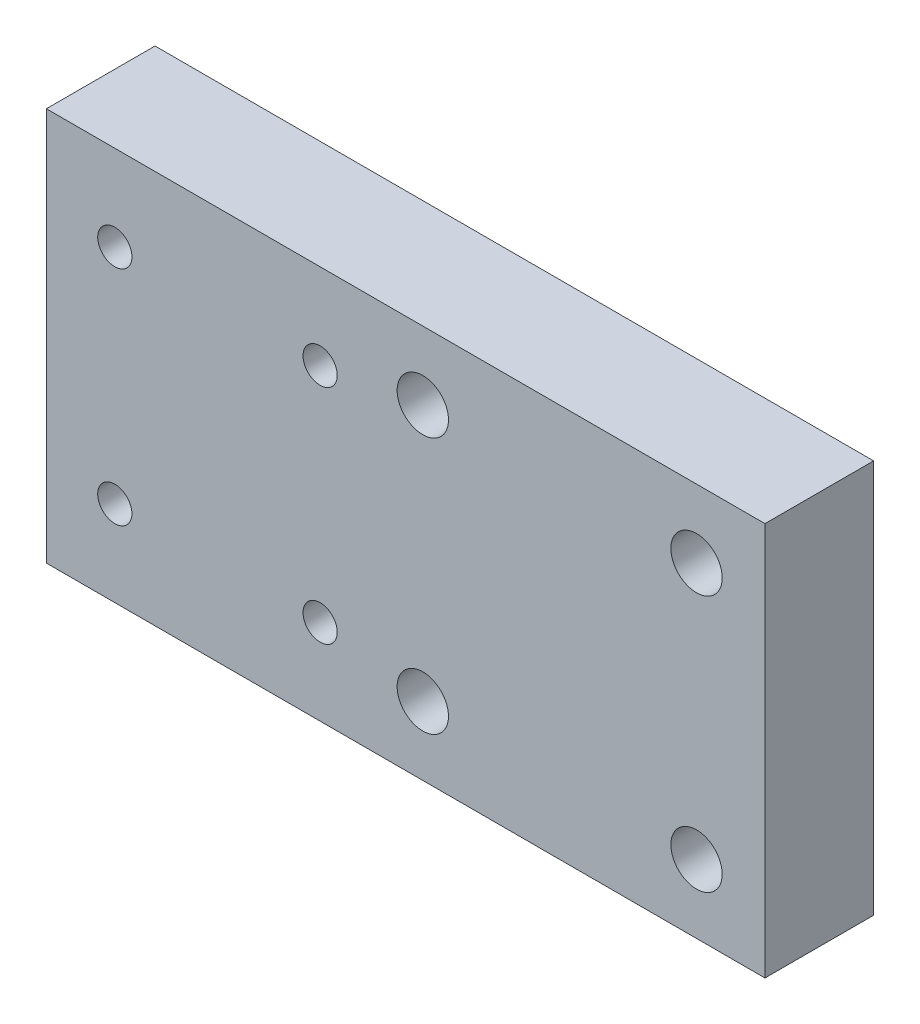
SolidWorks part; units mm, degrees
ref_plane "Front Plane" through (0, 0, 0) normal (0, 0, 1) x (1, 0, 0)
ref_plane "Top Plane" through (0, 0, 0) normal (0, 1, 0) x (1, 0, 0)
ref_plane "Right Plane" through (0, 0, 0) normal (1, 0, 0) x (0, 0, -1)
sketch "Sketch1" plane through (0, 0, 0) normal (0, 0, 1) x (1, 0, 0)
  line L0 (-8, 7.5) -> (8, 7.5) construction
  line L5 (-26, 6.5) -> (-14, 6.5) construction
  line L7 (-8, -7.5) -> (8, -7.5) construction
  line L8 (-8, -7.5) -> (-8, 7.5) construction
  line L9 (-8, 7.5) -> (8, 7.5) construction
  line L10 (8, -7.5) -> (8, 7.5) construction
  line L11 (-8, -7.5) -> (8, 7.5) construction
  line L12 (-8, 7.5) -> (8, -7.5) construction
  line L13 (-8, 7.5) -> (-8, -7.5) construction
  line L14 (-26, -6.5) -> (-14, -6.5) construction
  line L15 (-26, -6.5) -> (-26, 6.5) construction
  line L16 (-26, 6.5) -> (-14, 6.5) construction
  line L17 (-14, -6.5) -> (-14, 6.5) construction
  line L18 (-26, -6.5) -> (-14, 6.5) construction
  line L19 (-26, 6.5) -> (-14, -6.5) construction
  line L20 (0, 0) -> (-20, 0) construction
  line L22 (-30, -11.5) -> (12, -11.5)
  line L23 (-30, -11.5) -> (-30, 11.5)
  line L24 (-30, 11.5) -> (12, 11.5)
  line L25 (12, -11.5) -> (12, 11.5)
  line L26 (-30, -11.5) -> (12, 11.5) construction
  line L27 (-30, 11.5) -> (12, -11.5) construction
  line L28 (-11.5, -15) -> (-28.5, -15) construction
  line L29 (-11.5, -15) -> (-11.5, 15) construction
  line L30 (-11.5, 15) -> (-28.5, 15) construction
  line L31 (-28.5, -15) -> (-28.5, 15) construction
  line L32 (-11.5, -15) -> (-28.5, 15) construction
  line L33 (-11.5, 15) -> (-28.5, -15) construction
  circle A0 centre (-8, 7.5) radius 1.5
  circle A2 centre (8, 7.5) radius 1.5
  circle A3 centre (8, -7.5) radius 1.5
  circle A4 centre (-8, -7.5) radius 1.5
  circle A5 centre (-26, 6.5) radius 1
  circle A6 centre (-14, 6.5) radius 1
  circle A7 centre (-14, -6.5) radius 1
  circle A8 centre (-26, -6.5) radius 1
  circle A9 centre (-8, 7.5) radius 2.9 construction
  point P0 (0, 0)
  point P1 (-20, 0)
  point P4 (-9, 0)
  point P6 (0, 0)
  dimension "D5" = 3
  dimension "D6" = 2
  dimension "D18" = 5.8
  dimension "D1" = 15
  dimension "D2" = 16
  dimension "D3" = 13
  dimension "D4" = 12
  dimension "D9" = 16
  dimension "D10" = 15
  dimension "D13" = 12
  dimension "D14" = 20
  dimension "D15" = 23
  dimension "D16" = 4
  dimension "D17" = 4
  dimension "D19" = 17
  dimension "D20" = 30
  dimension "D7" = 2
  dimension "D8" = 2
  dimension "D11" = 2
  dimension "D12" = 2
extrude "Boss-Extrude1" add sketch "Sketch1" along normal blind 6.35
